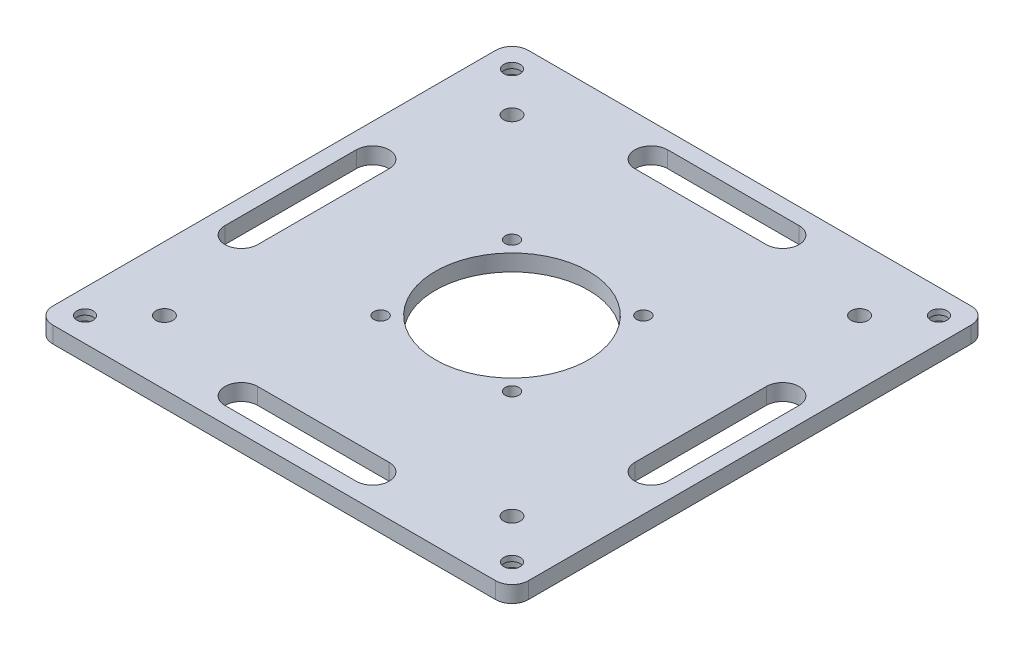
SolidWorks part; units mm, degrees
ref_plane "前基準面" through (0, 0, 0) normal (0, 0, 1) x (1, 0, 0)
ref_plane "上基準面" through (0, 0, 0) normal (0, 1, 0) x (1, 0, 0)
ref_plane "右基準面" through (0, 0, 0) normal (1, 0, 0) x (0, 0, -1)
ref_plane "平面1" through (0, -37, 0) normal (0, 1, 0) x (1, 0, 0)
sketch "草圖1" plane through (0, -37, 0) normal (0, 1, 0) x (1, 0, 0)
  line L0 (-43.45, -43.45) -> (43.45, -43.45)
  line L1 (43.45, -43.45) -> (43.45, 43.45)
  line L2 (43.45, 43.45) -> (-43.45, 43.45)
  line L3 (-43.45, 43.45) -> (-43.45, -43.45)
extrude "填料-伸長1" add sketch "草圖1" against normal blind 3
hole_wizard "M2.5 六角頭機械螺釘的柱孔1" positions "草圖3" profile "草圖2" counterbore size "M2.5" standard "Ansi Metric"
sketch "草圖3" plane through (0, -40, 0) normal (0, -1, 0) x (-1, 0, 0)
  point P0 (39, 39)
  point P1 (-39, 39)
  point P2 (-39, -39)
  point P3 (39, -39)
sketch "草圖2" plane through (-39, -40, -39) normal (1, 0, 0) x (0, 0, -1)
  line L0 (0, 0) -> (0, 3)
  line L1 (0, 3) -> (1.5, 3)
  line L3 (1.5, 3) -> (1.5, 2)
  line L4 (1.5, 2) -> (3, 2)
  line L5 (3, 2) -> (3, 0)
  line L7 (3, 0) -> (0, 0)
  line L11 (0, -6.35) -> (0, 107.95) construction
  dimension "砮 ふ 畖" = 3
  dimension "砮 ふ瞏 " = 3
  dimension "琖ふ 畖" = 6
  dimension "琖ふ瞏 " = 2
hole_wizard "Ø2.0 (2) 直徑孔1" positions "草圖5" profile "草圖4" hole size "Ø2.0" standard "Ansi Metric"
sketch "草圖5" plane through (0, -37, 0) normal (0, 1, 0) x (1, 0, 0)
  point P0 (5, -10)
  point P1 (0, -10)
  point P2 (-5, -10)
  point P3 (-10, -5)
  point P4 (-10, 0)
  point P5 (-10, 5)
  point P6 (-5, 10)
  point P7 (0, 10)
  point P8 (5, 10)
  point P9 (10, 5)
  point P10 (10, 0)
  point P11 (10, -5)
  point P12 (5, -5)
  point P13 (0, -5)
  point P14 (-5, -5)
  point P15 (-5, 0)
  point P16 (-5, 5)
  point P17 (0, 5)
  point P18 (5, 5)
  point P19 (5, 0)
  point P20 (0, 0)
  point P21 (-37.5, 3)
  point P22 (-37.5, 0)
  point P23 (-37.5, -3)
  point P24 (3, 37.5)
  point P25 (0, 37.5)
  point P26 (-3, 37.5)
  point P27 (37.5, -3)
  point P28 (37.5, 0)
  point P29 (37.5, 3)
  point P30 (-3, -37.5)
  point P31 (0, -37.5)
  point P32 (3, -37.5)
sketch "草圖4" plane through (5, -37, 10) normal (1, 0, 0) x (0, 0, 1)
  line L0 (0, 0) -> (0, 3)
  line L1 (0, 3) -> (1, 3)
  line L2 (1, 3) -> (1, 0)
  line L5 (1, 0) -> (0, 0)
  line L11 (0, -6.35) -> (0, 107.95) construction
  dimension "砮 ふ 畖" = 2
  dimension "砮 ふ瞏 " = 3
hole_wizard "Ø2.5 (2.5) 直徑孔1" positions "草圖7" profile "草圖6" hole size "Ø2.5" standard "Ansi Metric"
sketch "草圖7" plane through (0, -40, 0) normal (0, -1, 0) x (-1, 0, 0)
  point P0 (12, 12)
  point P1 (-12, 12)
  point P2 (12, -12)
  point P3 (-12, -12)
sketch "草圖6" plane through (-12, -40, -12) normal (1, 0, 0) x (0, 0, -1)
  line L0 (0, 0) -> (0, 3)
  line L1 (0, 3) -> (1.25, 3)
  line L2 (1.25, 3) -> (1.25, 0)
  line L5 (1.25, 0) -> (0, 0)
  line L11 (0, -6.35) -> (0, 107.95) construction
  dimension "砮 ふ 畖" = 2.5
  dimension "砮 ふ瞏 " = 3
fillet "圓角1" radius 3 4 edges at (-43.45, -38.5, 43.45) (-43.45, -38.5, -43.45) (43.45, -38.5, 43.45) (43.45, -38.5, -43.45) tangent propagation no
sketch "草圖8" plane through (0, -37, 0) normal (0, 1, 0) x (1, 0, 0)
  line L0 (-37.45, -12) -> (-37.45, 12) construction
  line L1 (-40.45, -12) -> (-40.45, 12)
  line L2 (-34.45, -12) -> (-34.45, 12)
  line L4 (-43.45, 40.45) -> (-43.45, -40.45) construction
  line L5 (0, 0) -> (-43.45, 0) construction
  line L6 (-12, 37.45) -> (12, 37.45) construction
  line L7 (-12, 40.45) -> (12, 40.45)
  line L8 (-12, 34.45) -> (12, 34.45)
  line L9 (37.45, 12) -> (37.45, -12) construction
  line L10 (40.45, 12) -> (40.45, -12)
  line L11 (34.45, 12) -> (34.45, -12)
  line L12 (12, -37.45) -> (-12, -37.45) construction
  line L13 (12, -40.45) -> (-12, -40.45)
  line L14 (12, -34.45) -> (-12, -34.45)
  circle A0 centre (0, 0) radius 14
  arc A1 (-40.45, -12) -> (-34.45, -12) centre (-37.45, -12) ccw
  arc A2 (-34.45, 12) -> (-40.45, 12) centre (-37.45, 12) ccw
  arc A4 (-12, 40.45) -> (-12, 34.45) centre (-12, 37.45) ccw
  arc A5 (12, 34.45) -> (12, 40.45) centre (12, 37.45) ccw
  arc A6 (40.45, 12) -> (34.45, 12) centre (37.45, 12) ccw
  arc A7 (34.45, -12) -> (40.45, -12) centre (37.45, -12) ccw
  arc A8 (12, -40.45) -> (12, -34.45) centre (12, -37.45) ccw
  arc A9 (-12, -34.45) -> (-12, -40.45) centre (-12, -37.45) ccw
  point P6 (-37.45, 0)
  point P21 (0, 37.45)
  point P28 (37.45, 0)
  point P35 (0, -37.45)
  point P40 (0, 0)
  dimension "D1" = 28
  dimension "D2" = 6
  dimension "D3" = 6
  dimension "D4" = 24
  dimension "D5" = 4
extrude "除料-伸長1" cut sketch "草圖8" against normal through all
sketch "草圖9" plane through (0, -37, 0) normal (0, 1, 0) x (1, 0, 0)
  line L0 (0, 0) -> (0, 43.45) construction
  line L1 (40.45, 43.45) -> (-40.45, 43.45) construction
  line L2 (-43.45, 0) -> (0, 0) construction
  line L3 (-43.45, 40.45) -> (-43.45, -40.45) construction
  circle A0 centre (-31.75, 31.75) radius 1.55
  circle A1 centre (31.75, 31.75) radius 1.55
  circle A2 centre (-31.75, -31.75) radius 1.55
  circle A3 centre (31.75, -31.75) radius 1.55
  point P16 (0, 0)
  point P17 (0, 0)
  point P18 (0, 0)
  point P19 (0, 0)
  dimension "D1" = 63.5
  dimension "D2" = 3.1
  dimension "D3" = 63.5
extrude "除料-伸長2" cut sketch "草圖9" against normal through all
